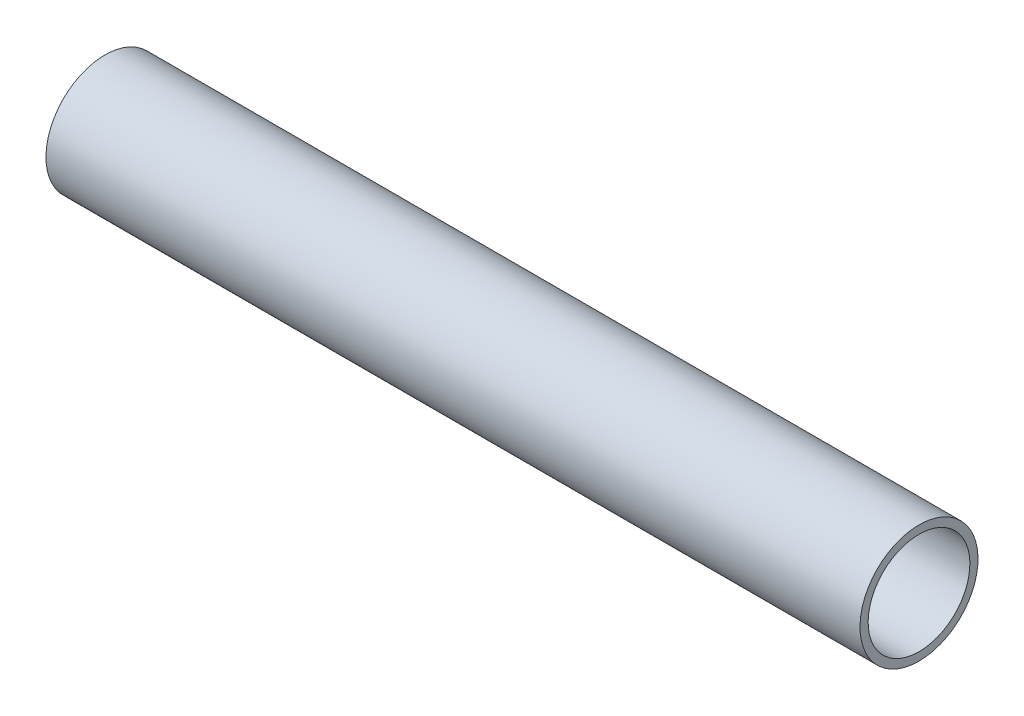
SolidWorks part; units mm, degrees
material "Hexcel AS4C (3000 Filaments)"
ref_plane "Front Plane" through (0, 0, 0) normal (0, 0, 1) x (1, 0, 0)
ref_plane "Top Plane" through (0, 0, 0) normal (0, 1, 0) x (1, 0, 0)
ref_plane "Right Plane" through (0, 0, 0) normal (1, 0, 0) x (0, 0, -1)
sketch "Sketch1" plane through (-15.5279, 0, 0) normal (-1, 0, 0) x (0, 0, 1)
  circle A0 centre (50, 105.8696) radius 12.5 construction
  circle A1 centre (50, 105.8696) radius 12.5
  circle A2 centre (50, 105.8696) radius 14.5
  dimension "D1" = 2
extrude "Boss-Extrude1" add sketch "Sketch1" against normal mid plane 200
equation "\"inner_fuselage_width\"=200"
equation "\"D1@Boss-Extrude1\"=\"inner_fuselage_width\""
